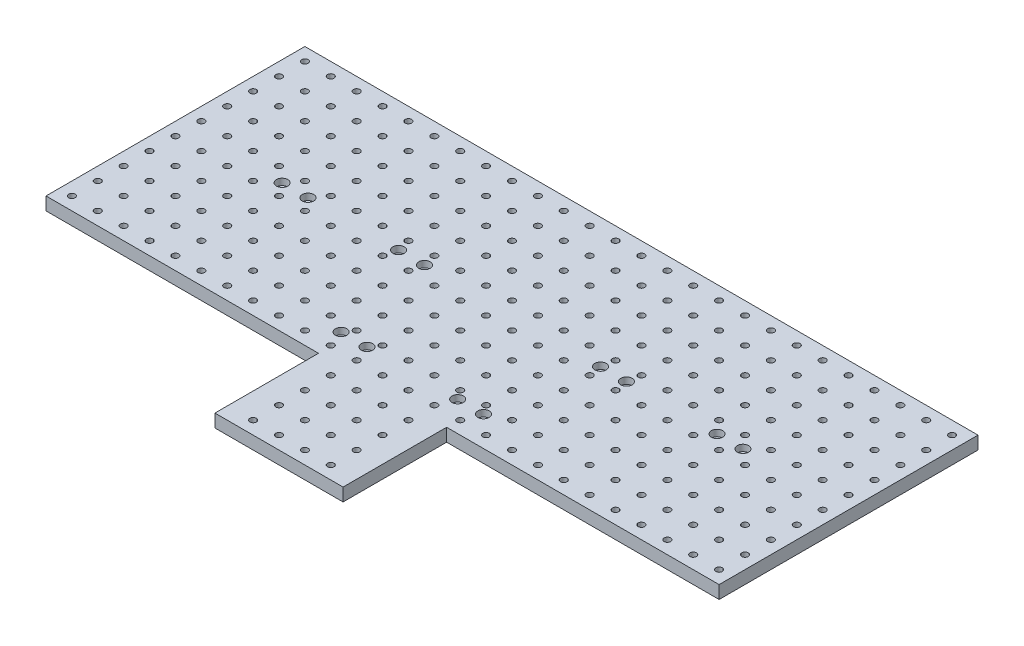
SolidWorks part; units mm, degrees
ref_plane "Front Plane" through (0, 0, 0) normal (0, 0, 1) x (1, 0, 0)
ref_plane "Top Plane" through (0, 0, 0) normal (0, 1, 0) x (1, 0, 0)
ref_plane "Right Plane" through (0, 0, 0) normal (1, 0, 0) x (0, 0, -1)
sketch "Sketch1" plane through (0, 0, 0) normal (0, 1, 0) x (1, 0, 0)
  line L0 (393.065, 0) -> (660.4, 0)
  line L1 (0, 0) -> (267.335, 0)
  line L2 (0, 0) -> (0, 254)
  line L3 (0, 254) -> (660.4, 254)
  line L4 (660.4, 0) -> (660.4, 254)
  line L6 (267.335, 0) -> (267.335, -101.6)
  line L7 (267.335, -101.6) -> (393.065, -101.6)
  line L8 (393.065, 0) -> (393.065, -101.6)
  circle A0 centre (12.7, 241.3) radius 3.175
  circle A1 centre (38.1, 241.3) radius 3.175
  circle A2 centre (63.5, 241.3) radius 3.175
  circle A3 centre (88.9, 241.3) radius 3.175
  circle A4 centre (114.3, 241.3) radius 3.175
  circle A5 centre (139.7, 241.3) radius 3.175
  circle A6 centre (165.1, 241.3) radius 3.175
  circle A7 centre (190.5, 241.3) radius 3.175
  circle A8 centre (215.9, 241.3) radius 3.175
  circle A9 centre (241.3, 241.3) radius 3.175
  circle A10 centre (266.7, 241.3) radius 3.175
  circle A11 centre (292.1, 241.3) radius 3.175
  circle A12 centre (317.5, 241.3) radius 3.175
  circle A13 centre (342.9, 241.3) radius 3.175
  circle A14 centre (368.3, 241.3) radius 3.175
  circle A15 centre (393.7, 241.3) radius 3.175
  circle A16 centre (419.1, 241.3) radius 3.175
  circle A17 centre (444.5, 241.3) radius 3.175
  circle A18 centre (469.9, 241.3) radius 3.175
  circle A19 centre (495.3, 241.3) radius 3.175
  circle A20 centre (520.7, 241.3) radius 3.175
  circle A21 centre (546.1, 241.3) radius 3.175
  circle A22 centre (571.5, 241.3) radius 3.175
  circle A23 centre (596.9, 241.3) radius 3.175
  circle A24 centre (622.3, 241.3) radius 3.175
  circle A25 centre (647.7, 241.3) radius 3.175
  circle A26 centre (38.1, 215.9) radius 3.175
  circle A27 centre (63.5, 215.9) radius 3.175
  circle A28 centre (88.9, 215.9) radius 3.175
  circle A29 centre (114.3, 215.9) radius 3.175
  circle A30 centre (139.7, 215.9) radius 3.175
  circle A31 centre (165.1, 215.9) radius 3.175
  circle A32 centre (190.5, 215.9) radius 3.175
  circle A33 centre (215.9, 215.9) radius 3.175
  circle A34 centre (241.3, 215.9) radius 3.175
  circle A35 centre (266.7, 215.9) radius 3.175
  circle A36 centre (292.1, 215.9) radius 3.175
  circle A37 centre (317.5, 215.9) radius 3.175
  circle A38 centre (342.9, 215.9) radius 3.175
  circle A39 centre (368.3, 215.9) radius 3.175
  circle A40 centre (393.7, 215.9) radius 3.175
  circle A41 centre (419.1, 215.9) radius 3.175
  circle A42 centre (444.5, 215.9) radius 3.175
  circle A43 centre (469.9, 215.9) radius 3.175
  circle A44 centre (495.3, 215.9) radius 3.175
  circle A45 centre (520.7, 215.9) radius 3.175
  circle A46 centre (546.1, 215.9) radius 3.175
  circle A47 centre (571.5, 215.9) radius 3.175
  circle A48 centre (596.9, 215.9) radius 3.175
  circle A49 centre (622.3, 215.9) radius 3.175
  circle A50 centre (647.7, 215.9) radius 3.175
  circle A51 centre (38.1, 190.5) radius 3.175
  circle A52 centre (63.5, 190.5) radius 3.175
  circle A53 centre (88.9, 190.5) radius 3.175
  circle A54 centre (114.3, 190.5) radius 3.175
  circle A55 centre (139.7, 190.5) radius 3.175
  circle A56 centre (165.1, 190.5) radius 3.175
  circle A57 centre (190.5, 190.5) radius 3.175
  circle A58 centre (215.9, 190.5) radius 3.175
  circle A59 centre (241.3, 190.5) radius 3.175
  circle A60 centre (266.7, 190.5) radius 3.175
  circle A61 centre (292.1, 190.5) radius 3.175
  circle A62 centre (317.5, 190.5) radius 3.175
  circle A63 centre (342.9, 190.5) radius 3.175
  circle A64 centre (368.3, 190.5) radius 3.175
  circle A65 centre (393.7, 190.5) radius 3.175
  circle A66 centre (419.1, 190.5) radius 3.175
  circle A67 centre (444.5, 190.5) radius 3.175
  circle A68 centre (469.9, 190.5) radius 3.175
  circle A69 centre (495.3, 190.5) radius 3.175
  circle A70 centre (520.7, 190.5) radius 3.175
  circle A71 centre (546.1, 190.5) radius 3.175
  circle A72 centre (571.5, 190.5) radius 3.175
  circle A73 centre (596.9, 190.5) radius 3.175
  circle A74 centre (622.3, 190.5) radius 3.175
  circle A75 centre (647.7, 190.5) radius 3.175
  circle A76 centre (38.1, 165.1) radius 3.175
  circle A77 centre (63.5, 165.1) radius 3.175
  circle A78 centre (88.9, 165.1) radius 3.175
  circle A79 centre (114.3, 165.1) radius 3.175
  circle A80 centre (139.7, 165.1) radius 3.175
  circle A81 centre (165.1, 165.1) radius 3.175
  circle A82 centre (190.5, 165.1) radius 3.175
  circle A83 centre (215.9, 165.1) radius 3.175
  circle A84 centre (241.3, 165.1) radius 3.175
  circle A85 centre (266.7, 165.1) radius 3.175
  circle A86 centre (292.1, 165.1) radius 3.175
  circle A87 centre (317.5, 165.1) radius 3.175
  circle A88 centre (342.9, 165.1) radius 3.175
  circle A89 centre (368.3, 165.1) radius 3.175
  circle A90 centre (393.7, 165.1) radius 3.175
  circle A91 centre (419.1, 165.1) radius 3.175
  circle A92 centre (444.5, 165.1) radius 3.175
  circle A93 centre (469.9, 165.1) radius 3.175
  circle A94 centre (495.3, 165.1) radius 3.175
  circle A95 centre (520.7, 165.1) radius 3.175
  circle A96 centre (546.1, 165.1) radius 3.175
  circle A97 centre (571.5, 165.1) radius 3.175
  circle A98 centre (596.9, 165.1) radius 3.175
  circle A99 centre (622.3, 165.1) radius 3.175
  circle A100 centre (647.7, 165.1) radius 3.175
  circle A101 centre (38.1, 139.7) radius 3.175
  circle A102 centre (63.5, 139.7) radius 3.175
  circle A103 centre (88.9, 139.7) radius 3.175
  circle A104 centre (114.3, 139.7) radius 3.175
  circle A105 centre (139.7, 139.7) radius 3.175
  circle A106 centre (165.1, 139.7) radius 3.175
  circle A107 centre (190.5, 139.7) radius 3.175
  circle A108 centre (215.9, 139.7) radius 3.175
  circle A109 centre (241.3, 139.7) radius 3.175
  circle A110 centre (266.7, 139.7) radius 3.175
  circle A111 centre (292.1, 139.7) radius 3.175
  circle A112 centre (317.5, 139.7) radius 3.175
  circle A113 centre (342.9, 139.7) radius 3.175
  circle A114 centre (368.3, 139.7) radius 3.175
  circle A115 centre (393.7, 139.7) radius 3.175
  circle A116 centre (419.1, 139.7) radius 3.175
  circle A117 centre (444.5, 139.7) radius 3.175
  circle A118 centre (469.9, 139.7) radius 3.175
  circle A119 centre (495.3, 139.7) radius 3.175
  circle A120 centre (520.7, 139.7) radius 3.175
  circle A121 centre (546.1, 139.7) radius 3.175
  circle A122 centre (571.5, 139.7) radius 3.175
  circle A123 centre (596.9, 139.7) radius 3.175
  circle A124 centre (622.3, 139.7) radius 3.175
  circle A125 centre (647.7, 139.7) radius 3.175
  circle A126 centre (38.1, 114.3) radius 3.175
  circle A127 centre (63.5, 114.3) radius 3.175
  circle A128 centre (88.9, 114.3) radius 3.175
  circle A129 centre (114.3, 114.3) radius 3.175
  circle A130 centre (139.7, 114.3) radius 3.175
  circle A131 centre (165.1, 114.3) radius 3.175
  circle A132 centre (190.5, 114.3) radius 3.175
  circle A133 centre (215.9, 114.3) radius 3.175
  circle A134 centre (241.3, 114.3) radius 3.175
  circle A135 centre (266.7, 114.3) radius 3.175
  circle A136 centre (292.1, 114.3) radius 3.175
  circle A137 centre (317.5, 114.3) radius 3.175
  circle A138 centre (342.9, 114.3) radius 3.175
  circle A139 centre (368.3, 114.3) radius 3.175
  circle A140 centre (393.7, 114.3) radius 3.175
  circle A141 centre (419.1, 114.3) radius 3.175
  circle A142 centre (444.5, 114.3) radius 3.175
  circle A143 centre (469.9, 114.3) radius 3.175
  circle A144 centre (495.3, 114.3) radius 3.175
  circle A145 centre (520.7, 114.3) radius 3.175
  circle A146 centre (546.1, 114.3) radius 3.175
  circle A147 centre (571.5, 114.3) radius 3.175
  circle A148 centre (596.9, 114.3) radius 3.175
  circle A149 centre (622.3, 114.3) radius 3.175
  circle A150 centre (647.7, 114.3) radius 3.175
  circle A151 centre (38.1, 88.9) radius 3.175
  circle A152 centre (63.5, 88.9) radius 3.175
  circle A153 centre (88.9, 88.9) radius 3.175
  circle A154 centre (114.3, 88.9) radius 3.175
  circle A155 centre (139.7, 88.9) radius 3.175
  circle A156 centre (165.1, 88.9) radius 3.175
  circle A157 centre (190.5, 88.9) radius 3.175
  circle A158 centre (215.9, 88.9) radius 3.175
  circle A159 centre (241.3, 88.9) radius 3.175
  circle A160 centre (266.7, 88.9) radius 3.175
  circle A161 centre (292.1, 88.9) radius 3.175
  circle A162 centre (317.5, 88.9) radius 3.175
  circle A163 centre (342.9, 88.9) radius 3.175
  circle A164 centre (368.3, 88.9) radius 3.175
  circle A165 centre (393.7, 88.9) radius 3.175
  circle A166 centre (419.1, 88.9) radius 3.175
  circle A167 centre (444.5, 88.9) radius 3.175
  circle A168 centre (469.9, 88.9) radius 3.175
  circle A169 centre (495.3, 88.9) radius 3.175
  circle A170 centre (520.7, 88.9) radius 3.175
  circle A171 centre (546.1, 88.9) radius 3.175
  circle A172 centre (571.5, 88.9) radius 3.175
  circle A173 centre (596.9, 88.9) radius 3.175
  circle A174 centre (622.3, 88.9) radius 3.175
  circle A175 centre (647.7, 88.9) radius 3.175
  circle A176 centre (38.1, 63.5) radius 3.175
  circle A177 centre (63.5, 63.5) radius 3.175
  circle A178 centre (88.9, 63.5) radius 3.175
  circle A179 centre (114.3, 63.5) radius 3.175
  circle A180 centre (139.7, 63.5) radius 3.175
  circle A181 centre (165.1, 63.5) radius 3.175
  circle A182 centre (190.5, 63.5) radius 3.175
  circle A183 centre (215.9, 63.5) radius 3.175
  circle A184 centre (241.3, 63.5) radius 3.175
  circle A185 centre (266.7, 63.5) radius 3.175
  circle A186 centre (292.1, 63.5) radius 3.175
  circle A187 centre (317.5, 63.5) radius 3.175
  circle A188 centre (342.9, 63.5) radius 3.175
  circle A189 centre (368.3, 63.5) radius 3.175
  circle A190 centre (393.7, 63.5) radius 3.175
  circle A191 centre (419.1, 63.5) radius 3.175
  circle A192 centre (444.5, 63.5) radius 3.175
  circle A193 centre (469.9, 63.5) radius 3.175
  circle A194 centre (495.3, 63.5) radius 3.175
  circle A195 centre (520.7, 63.5) radius 3.175
  circle A196 centre (546.1, 63.5) radius 3.175
  circle A197 centre (571.5, 63.5) radius 3.175
  circle A198 centre (596.9, 63.5) radius 3.175
  circle A199 centre (622.3, 63.5) radius 3.175
  circle A200 centre (647.7, 63.5) radius 3.175
  circle A201 centre (38.1, 38.1) radius 3.175
  circle A202 centre (63.5, 38.1) radius 3.175
  circle A203 centre (88.9, 38.1) radius 3.175
  circle A204 centre (114.3, 38.1) radius 3.175
  circle A205 centre (139.7, 38.1) radius 3.175
  circle A206 centre (165.1, 38.1) radius 3.175
  circle A207 centre (190.5, 38.1) radius 3.175
  circle A208 centre (215.9, 38.1) radius 3.175
  circle A209 centre (241.3, 38.1) radius 3.175
  circle A210 centre (266.7, 38.1) radius 3.175
  circle A211 centre (292.1, 38.1) radius 3.175
  circle A212 centre (317.5, 38.1) radius 3.175
  circle A213 centre (342.9, 38.1) radius 3.175
  circle A214 centre (368.3, 38.1) radius 3.175
  circle A215 centre (393.7, 38.1) radius 3.175
  circle A216 centre (419.1, 38.1) radius 3.175
  circle A217 centre (444.5, 38.1) radius 3.175
  circle A218 centre (469.9, 38.1) radius 3.175
  circle A219 centre (495.3, 38.1) radius 3.175
  circle A220 centre (520.7, 38.1) radius 3.175
  circle A221 centre (546.1, 38.1) radius 3.175
  circle A222 centre (571.5, 38.1) radius 3.175
  circle A223 centre (596.9, 38.1) radius 3.175
  circle A224 centre (622.3, 38.1) radius 3.175
  circle A225 centre (647.7, 38.1) radius 3.175
  circle A226 centre (38.1, 12.7) radius 3.175
  circle A227 centre (63.5, 12.7) radius 3.175
  circle A228 centre (88.9, 12.7) radius 3.175
  circle A229 centre (114.3, 12.7) radius 3.175
  circle A230 centre (139.7, 12.7) radius 3.175
  circle A231 centre (165.1, 12.7) radius 3.175
  circle A232 centre (190.5, 12.7) radius 3.175
  circle A233 centre (215.9, 12.7) radius 3.175
  circle A234 centre (241.3, 12.7) radius 3.175
  circle A235 centre (266.7, 12.7) radius 3.175
  circle A236 centre (292.1, 12.7) radius 3.175
  circle A237 centre (317.5, 12.7) radius 3.175
  circle A238 centre (342.9, 12.7) radius 3.175
  circle A239 centre (368.3, 12.7) radius 3.175
  circle A240 centre (393.7, 12.7) radius 3.175
  circle A241 centre (419.1, 12.7) radius 3.175
  circle A242 centre (444.5, 12.7) radius 3.175
  circle A243 centre (469.9, 12.7) radius 3.175
  circle A244 centre (495.3, 12.7) radius 3.175
  circle A245 centre (520.7, 12.7) radius 3.175
  circle A246 centre (546.1, 12.7) radius 3.175
  circle A247 centre (571.5, 12.7) radius 3.175
  circle A248 centre (596.9, 12.7) radius 3.175
  circle A249 centre (622.3, 12.7) radius 3.175
  circle A250 centre (647.7, 12.7) radius 3.175
  circle A261 centre (292.1, -12.7) radius 3.175
  circle A262 centre (317.5, -12.7) radius 3.175
  circle A263 centre (342.9, -12.7) radius 3.175
  circle A264 centre (368.3, -12.7) radius 3.175
  circle A286 centre (292.1, -38.1) radius 3.175
  circle A287 centre (317.5, -38.1) radius 3.175
  circle A288 centre (342.9, -38.1) radius 3.175
  circle A289 centre (368.3, -38.1) radius 3.175
  circle A311 centre (292.1, -63.5) radius 3.175
  circle A312 centre (317.5, -63.5) radius 3.175
  circle A313 centre (342.9, -63.5) radius 3.175
  circle A314 centre (368.3, -63.5) radius 3.175
  circle A336 centre (292.1, -88.9) radius 3.175
  circle A337 centre (317.5, -88.9) radius 3.175
  circle A338 centre (342.9, -88.9) radius 3.175
  circle A339 centre (368.3, -88.9) radius 3.175
  circle A351 centre (12.7, 215.9) radius 3.175
  circle A352 centre (12.7, 190.5) radius 3.175
  circle A353 centre (12.7, 165.1) radius 3.175
  circle A354 centre (12.7, 139.7) radius 3.175
  circle A355 centre (12.7, 114.3) radius 3.175
  circle A356 centre (12.7, 88.9) radius 3.175
  circle A357 centre (12.7, 63.5) radius 3.175
  circle A358 centre (12.7, 38.1) radius 3.175
  circle A359 centre (12.7, 12.7) radius 3.175
  circle A364 centre (38.1, -12.7) radius 3.175 [skipped]
  circle A365 centre (12.7, -12.7) radius 3.175 [skipped]
  circle A366 centre (63.5, -12.7) radius 3.175 [skipped]
  circle A367 centre (88.9, -12.7) radius 3.175 [skipped]
  circle A368 centre (114.3, -12.7) radius 3.175 [skipped]
  circle A369 centre (190.5, -12.7) radius 3.175 [skipped]
  circle A370 centre (215.9, -12.7) radius 3.175 [skipped]
  circle A371 centre (241.3, -12.7) radius 3.175 [skipped]
  circle A372 centre (165.1, -12.7) radius 3.175 [skipped]
  circle A373 centre (139.7, -12.7) radius 3.175 [skipped]
  circle A374 centre (38.1, -38.1) radius 3.175 [skipped]
  circle A375 centre (12.7, -38.1) radius 3.175 [skipped]
  circle A376 centre (63.5, -38.1) radius 3.175 [skipped]
  circle A377 centre (88.9, -38.1) radius 3.175 [skipped]
  circle A378 centre (114.3, -38.1) radius 3.175 [skipped]
  circle A379 centre (139.7, -38.1) radius 3.175 [skipped]
  circle A380 centre (165.1, -38.1) radius 3.175 [skipped]
  circle A381 centre (190.5, -38.1) radius 3.175 [skipped]
  circle A382 centre (215.9, -38.1) radius 3.175 [skipped]
  circle A383 centre (241.3, -38.1) radius 3.175 [skipped]
  circle A384 centre (241.3, -63.5) radius 3.175 [skipped]
  circle A385 centre (241.3, -88.9) radius 3.175 [skipped]
  circle A386 centre (215.9, -63.5) radius 3.175 [skipped]
  circle A387 centre (215.9, -88.9) radius 3.175 [skipped]
  circle A388 centre (190.5, -88.9) radius 3.175 [skipped]
  circle A389 centre (190.5, -63.5) radius 3.175 [skipped]
  circle A390 centre (165.1, -63.5) radius 3.175 [skipped]
  circle A391 centre (139.7, -63.5) radius 3.175 [skipped]
  circle A392 centre (139.7, -88.9) radius 3.175 [skipped]
  circle A393 centre (114.3, -88.9) radius 3.175 [skipped]
  circle A394 centre (12.7, -88.9) radius 3.175 [skipped]
  circle A395 centre (38.1, -88.9) radius 3.175 [skipped]
  circle A396 centre (63.5, -88.9) radius 3.175 [skipped]
  circle A397 centre (88.9, -88.9) radius 3.175 [skipped]
  circle A398 centre (114.3, -63.5) radius 3.175 [skipped]
  circle A399 centre (88.9, -63.5) radius 3.175 [skipped]
  circle A400 centre (63.5, -63.5) radius 3.175 [skipped]
  circle A401 centre (38.1, -63.5) radius 3.175 [skipped]
  circle A402 centre (12.7, -63.5) radius 3.175 [skipped]
  circle A403 centre (165.1, -88.9) radius 3.175 [skipped]
  circle A404 centre (647.7, -12.7) radius 3.175 [skipped]
  circle A405 centre (647.7, -38.1) radius 3.175 [skipped]
  circle A406 centre (647.7, -63.5) radius 3.175 [skipped]
  circle A407 centre (647.7, -88.9) radius 3.175 [skipped]
  circle A408 centre (622.3, -88.9) radius 3.175 [skipped]
  circle A409 centre (622.3, -63.5) radius 3.175 [skipped]
  circle A410 centre (622.3, -38.1) radius 3.175 [skipped]
  circle A411 centre (622.3, -12.7) radius 3.175 [skipped]
  circle A412 centre (596.9, -12.7) radius 3.175 [skipped]
  circle A413 centre (596.9, -38.1) radius 3.175 [skipped]
  circle A414 centre (596.9, -63.5) radius 3.175 [skipped]
  circle A415 centre (596.9, -88.9) radius 3.175 [skipped]
  circle A416 centre (571.5, -88.9) radius 3.175 [skipped]
  circle A417 centre (571.5, -38.1) radius 3.175 [skipped]
  circle A418 centre (571.5, -12.7) radius 3.175 [skipped]
  circle A419 centre (546.1, -12.7) radius 3.175 [skipped]
  circle A420 centre (546.1, -38.1) radius 3.175 [skipped]
  circle A421 centre (546.1, -63.5) radius 3.175 [skipped]
  circle A422 centre (546.1, -88.9) radius 3.175 [skipped]
  circle A423 centre (571.5, -63.5) radius 3.175 [skipped]
  circle A424 centre (520.7, -88.9) radius 3.175 [skipped]
  circle A425 centre (495.3, -88.9) radius 3.175 [skipped]
  circle A426 centre (444.5, -88.9) radius 3.175 [skipped]
  circle A427 centre (419.1, -88.9) radius 3.175 [skipped]
  circle A428 centre (419.1, -63.5) radius 3.175 [skipped]
  circle A429 centre (419.1, -38.1) radius 3.175 [skipped]
  circle A430 centre (419.1, -12.7) radius 3.175 [skipped]
  circle A431 centre (469.9, -12.7) radius 3.175 [skipped]
  circle A432 centre (520.7, -12.7) radius 3.175 [skipped]
  circle A433 centre (520.7, -38.1) radius 3.175 [skipped]
  circle A434 centre (520.7, -63.5) radius 3.175 [skipped]
  circle A435 centre (495.3, -63.5) radius 3.175 [skipped]
  circle A436 centre (444.5, -63.5) radius 3.175 [skipped]
  circle A437 centre (469.9, -63.5) radius 3.175 [skipped]
  circle A438 centre (469.9, -88.9) radius 3.175 [skipped]
  circle A439 centre (495.3, -38.1) radius 3.175 [skipped]
  circle A440 centre (495.3, -12.7) radius 3.175 [skipped]
  circle A441 centre (469.9, -38.1) radius 3.175 [skipped]
  circle A442 centre (444.5, -12.7) radius 3.175 [skipped]
  circle A443 centre (444.5, -38.1) radius 3.175 [skipped]
  arc A444 (267.335, -15.8109) -> (267.335, -9.5891) centre (266.7, -12.7) ccw [skipped]
  arc A445 (267.335, -41.2109) -> (267.335, -34.9891) centre (266.7, -38.1) ccw [skipped]
  arc A446 (267.335, -66.6109) -> (267.335, -60.3891) centre (266.7, -63.5) ccw [skipped]
  arc A447 (267.335, -92.0109) -> (267.335, -85.7891) centre (266.7, -88.9) ccw [skipped]
  arc A448 (393.065, -9.5891) -> (393.065, -15.8109) centre (393.7, -12.7) ccw [skipped]
  arc A449 (393.065, -34.9891) -> (393.065, -41.2109) centre (393.7, -38.1) ccw [skipped]
  arc A450 (393.065, -85.7891) -> (393.065, -92.0109) centre (393.7, -88.9) ccw [skipped]
  arc A451 (393.065, -60.3891) -> (393.065, -66.6109) centre (393.7, -63.5) ccw [skipped]
  dimension "D6" = 6.35
  dimension "D1" = 254
  dimension "D2" = 660.4
  dimension "D3" = 125.73
  dimension "D4" = 267.335
  dimension "D5" = 101.6
  dimension "D7" = 12.7
  dimension "D8" = 12.7
  dimension "D9" = 26
  dimension "D10" = 14
extrude "Boss-Extrude1" add sketch "Sketch1" along normal blind 12.7
sketch "Sketch2" plane through (0, 12.7, 0) normal (0, 1, 0) x (1, 0, 0)
  line L0 (660.4, 254) -> (0, 254) construction
  line L1 (267.335, -101.6) -> (393.065, -101.6) construction
  circle A0 centre (531.368, 127) radius 3.175
  circle A1 centre (531.368, 127) radius 5.588
  circle A2 centre (556.768, 127) radius 3.175
  circle A3 centre (556.768, 127) radius 5.588
  circle A4 centre (442.468, 127) radius 3.175
  circle A5 centre (442.468, 127) radius 5.588
  circle A6 centre (417.068, 127) radius 3.175
  circle A7 centre (417.068, 127) radius 5.588
  circle A8 centre (104.648, 127) radius 3.175
  circle A9 centre (104.648, 127) radius 5.588
  circle A10 centre (130.048, 127) radius 3.175
  circle A11 centre (130.048, 127) radius 5.588
  circle A12 centre (218.948, 127) radius 3.175
  circle A13 centre (218.948, 127) radius 5.588
  circle A14 centre (244.348, 127) radius 3.175
  circle A15 centre (244.348, 127) radius 5.588
  point P36 (330.2, -101.6)
  dimension "D1" = 6.35
  dimension "D2" = 11.176
  dimension "D3" = 25.4
  dimension "D4" = 25.4
  dimension "D5" = 25.4
  dimension "D6" = 25.4
  dimension "D7" = 127
  dimension "D8" = 88.9
  dimension "D9" = 88.9
  dimension "D10" = 85.852
  dimension "D11" = 86.868
extrude "Cut-Extrude1" cut sketch "Sketch2" against normal blind 6.35
extrude "Cut-Extrude2" cut sketch "Sketch2<2>" against normal blind 12.7 contours A8 | A10 | A12 | A14 | A6 | A4 | A0 | A2 region at (531.368, 12.7, -127) region at (556.768, 12.7, -127) region at (442.468, 12.7, -127) region at (417.068, 12.7, -127) region at (104.648, 12.7, -127) region at (130.048, 12.7, -127) region at (218.948, 12.7, -127) region at (244.348, 12.7, -127)
sketch "Sketch2<2>" plane through (0, 12.7, 0) normal (0, 1, 0) x (1, 0, 0) same geometry as "Sketch2"
sketch "Sketch3" plane through (0, 12.7, 0) normal (0, 1, 0) x (1, 0, 0)
  line L1 (267.335, -101.6) -> (393.065, -101.6) construction
  circle A0 centre (260.35, 29.21) radius 3.175
  circle A1 centre (260.35, 29.21) radius 5.588
  circle A2 centre (285.75, 29.21) radius 3.175
  circle A3 centre (285.75, 29.21) radius 5.588
  circle A4 centre (374.65, 29.21) radius 3.175
  circle A5 centre (374.65, 29.21) radius 5.588
  circle A6 centre (400.05, 29.21) radius 3.175
  circle A7 centre (400.05, 29.21) radius 5.588
  point P12 (330.2, -101.6)
  dimension "D1" = 6.35
  dimension "D2" = 11.176
  dimension "D3" = 25.4
  dimension "D4" = 25.4
  dimension "D5" = 130.81
  dimension "D6" = 88.9
  dimension "D7" = 44.45
extrude "Cut-Extrude3" cut sketch "Sketch3" against normal blind 6.35
extrude "Cut-Extrude4" cut sketch "Sketch3<2>" against normal blind 12.7 contours A4 | A0 | A2 | A6 region at (374.65, 12.7, -29.21)
sketch "Sketch3<2>" plane through (0, 12.7, 0) normal (0, 1, 0) x (1, 0, 0) same geometry as "Sketch3"
